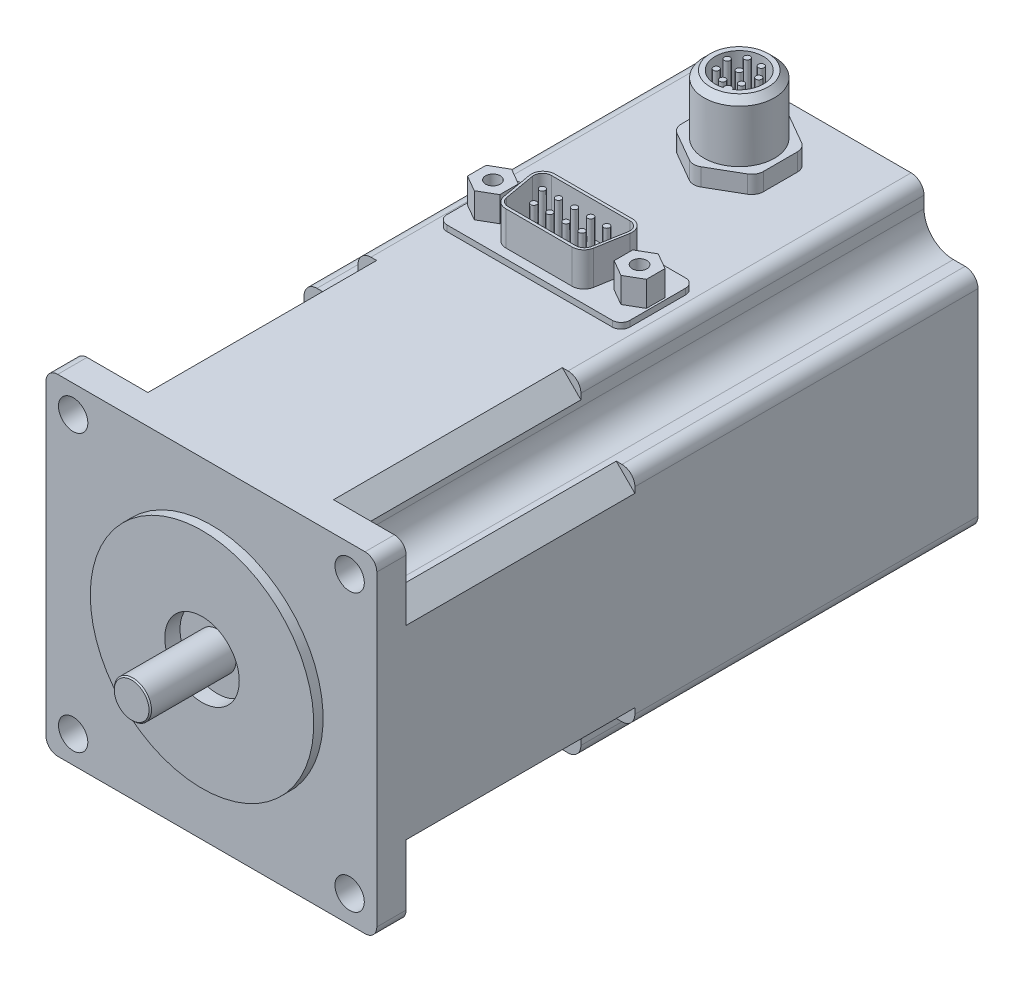
SolidWorks part; units mm, degrees
ref_plane "Front Plane" through (0, 0, 0) normal (0, 0, 1) x (1, 0, 0)
ref_plane "Top Plane" through (0, 0, 0) normal (0, 1, 0) x (1, 0, 0)
ref_plane "Right Plane" through (0, 0, 0) normal (1, 0, 0) x (0, 0, -1)
sketch "Sketch1" plane through (0, 0, 0) normal (0, 1, 0) x (1, 0, 0)
  line L0 (0, 0) -> (19.05, 0)
  line L1 (19.05, 0) -> (19.05, -1.6)
  line L2 (19.05, -1.6) -> (3.175, -1.6)
  line L3 (3.175, -1.6) -> (3.175, -13.6)
  line L4 (3.175, -13.6) -> (0, -13.6)
  line L5 (0, -13.6) -> (0, 0)
  line L6 (0, -13.6) -> (0, 0) construction
revolve "Revolve1" add sketch "Sketch1" angle 360 about L6 reverse direction yes
sketch "Sketch2" plane through (0, 0, 0) normal (0, 0, 1) x (1, 0, 0)
  line L0 (-26.2, -28.2) -> (26.2, -28.2)
  line L1 (28.2, -26.2) -> (28.2, 26.2)
  line L2 (26.2, 28.2) -> (-26.2, 28.2)
  line L3 (-28.2, 26.2) -> (-28.2, -26.2)
  arc A0 (-28.2, -26.2) -> (-26.2, -28.2) centre (-26.2, -26.2) ccw
  arc A1 (26.2, -28.2) -> (28.2, -26.2) centre (26.2, -26.2) ccw
  arc A2 (28.2, 26.2) -> (26.2, 28.2) centre (26.2, 26.2) ccw
  arc A3 (-26.2, 28.2) -> (-28.2, 26.2) centre (-26.2, 26.2) ccw
extrude "Boss-Extrude1" add sketch "Sketch2" against normal blind 70.5
ref_plane "Plane1" through (0, 0, -5) normal (0, 0, 1) x (1, 0, 0)
sketch "Sketch3" plane through (0, 0, -5) normal (0, 0, 1) x (1, 0, 0)
  line L0 (-37.6, -37.6) -> (37.6, -37.6)
  line L1 (37.6, -37.6) -> (37.6, 37.6)
  line L2 (37.6, 37.6) -> (-37.6, 37.6)
  line L3 (-37.6, 37.6) -> (-37.6, -37.6)
  line L4 (-26, -19) -> (-24, -19)
  line L5 (-19, -24) -> (-19, -26)
  line L6 (-16.8, -28.2) -> (16.8, -28.2)
  line L7 (19, -26) -> (19, -24)
  line L8 (24, -19) -> (26, -19)
  line L9 (28.2, -16.8) -> (28.2, 16.8)
  line L10 (26, 19) -> (24, 19)
  line L11 (19, 24) -> (19, 26)
  line L12 (16.8, 28.2) -> (-16.8, 28.2)
  line L13 (-19, 26) -> (-19, 24)
  line L14 (-24, 19) -> (-26, 19)
  line L15 (-28.2, 16.8) -> (-28.2, -16.8)
  arc A0 (-28.2, -16.8) -> (-26, -19) centre (-26, -16.8) ccw
  arc A1 (-24, -19) -> (-19, -24) centre (-24, -24) cw
  arc A2 (-19, -26) -> (-16.8, -28.2) centre (-16.8, -26) ccw
  arc A3 (16.8, -28.2) -> (19, -26) centre (16.8, -26) ccw
  arc A4 (19, -24) -> (24, -19) centre (24, -24) cw
  arc A5 (26, -19) -> (28.2, -16.8) centre (26, -16.8) ccw
  arc A6 (28.2, 16.8) -> (26, 19) centre (26, 16.8) ccw
  arc A7 (24, 19) -> (19, 24) centre (24, 24) cw
  arc A8 (19, 26) -> (16.8, 28.2) centre (16.8, 26) ccw
  arc A9 (-16.8, 28.2) -> (-19, 26) centre (-16.8, 26) ccw
  arc A10 (-19, 24) -> (-24, 19) centre (-24, 24) cw
  arc A11 (-26, 19) -> (-28.2, 16.8) centre (-26, 16.8) ccw
sketch "Sketch4" plane through (0, 0, 0) normal (0, 0, 1) x (1, 0, 0)
  circle A0 centre (23.57, -23.57) radius 2.5
extrude "Cut-Extrude1" cut sketch "Sketch4" against normal blind 5
sketch "Sketch5" plane through (0, 0, 0) normal (0, 0, 1) x (1, 0, 0)
  circle A0 centre (23.57, 23.57) radius 2.5
extrude "Cut-Extrude2" cut sketch "Sketch5" against normal blind 5
sketch "Sketch6" plane through (0, 0, 0) normal (0, 0, 1) x (1, 0, 0)
  circle A0 centre (-23.57, -23.57) radius 2.5
extrude "Cut-Extrude3" cut sketch "Sketch6" against normal blind 5
sketch "Sketch7" plane through (0, 0, 0) normal (0, 0, 1) x (1, 0, 0)
  circle A0 centre (-23.57, 23.57) radius 2.5
extrude "Cut-Extrude4" cut sketch "Sketch7" against normal blind 5
extrude "Cut-Extrude5" cut sketch "Sketch3" against normal blind 65.5
sketch "Sketch8" plane through (0, 0, -5) normal (0, 0, 1) x (1, 0, 0)
  line L0 (-37.6, 37.6) -> (-37.6, -37.6)
  line L1 (-37.6, -37.6) -> (37.6, -37.6)
  line L2 (37.6, -37.6) -> (37.6, 37.6)
  line L3 (37.6, 37.6) -> (-37.6, 37.6)
  line L4 (-28.2, -15.8256) -> (-15.8256, -28.2)
  line L5 (-15.8256, -28.2) -> (15.8256, -28.2)
  line L6 (15.8256, -28.2) -> (28.2, -15.8256)
  line L7 (28.2, -15.8256) -> (28.2, 15.8256)
  line L8 (28.2, 15.8256) -> (15.8256, 28.2)
  line L9 (15.8256, 28.2) -> (-15.8256, 28.2)
  line L10 (-15.8256, 28.2) -> (-28.2, 15.8256)
  line L11 (-28.2, 15.8256) -> (-28.2, -15.8256)
extrude "Cut-Extrude6" cut sketch "Sketch8" against normal blind 39
ref_plane "Plane2" through (0, 0, -70.5) normal (0, 0, 1) x (1, 0, 0)
sketch "Sketch9" plane through (0, 0, -70.5) normal (0, 0, 1) x (1, 0, 0)
  line L0 (-26, -19) -> (-24, -19)
  line L1 (-19, -24) -> (-19, -26)
  line L2 (-16.8, -28.2) -> (16.8, -28.2)
  line L3 (19, -26) -> (19, -24)
  line L4 (24, -19) -> (26, -19)
  line L5 (28.2, -16.8) -> (28.2, 16.8)
  line L6 (26, 19) -> (24, 19)
  line L7 (19, 24) -> (19, 26)
  line L8 (16.8, 28.2) -> (-16.8, 28.2)
  line L9 (-19, 26) -> (-19, 24)
  line L10 (-24, 19) -> (-26, 19)
  line L11 (-28.2, 16.8) -> (-28.2, -16.8)
  arc A0 (-28.2, -16.8) -> (-26, -19) centre (-26, -16.8) ccw
  arc A1 (-24, -19) -> (-19, -24) centre (-24, -24) cw
  arc A2 (-19, -26) -> (-16.8, -28.2) centre (-16.8, -26) ccw
  arc A3 (16.8, -28.2) -> (19, -26) centre (16.8, -26) ccw
  arc A4 (19, -24) -> (24, -19) centre (24, -24) cw
  arc A5 (26, -19) -> (28.2, -16.8) centre (26, -16.8) ccw
  arc A6 (28.2, 16.8) -> (26, 19) centre (26, 16.8) ccw
  arc A7 (24, 19) -> (19, 24) centre (24, 24) cw
  arc A8 (19, 26) -> (16.8, 28.2) centre (16.8, 26) ccw
  arc A9 (-16.8, 28.2) -> (-19, 26) centre (-16.8, 26) ccw
  arc A10 (-19, 24) -> (-24, 19) centre (-24, 24) cw
  arc A11 (-26, 19) -> (-28.2, 16.8) centre (-26, 16.8) ccw
extrude "Boss-Extrude2" add sketch "Sketch9" against normal blind 32
ref_plane "Plane3" through (0, 28.2, 0) normal (0, 1, 0) x (1, 0, 0)
sketch "Sketch10" plane through (0, 28.2, 0) normal (0, 1, 0) x (1, 0, 0)
  line L0 (-15.6, 65.25) -> (-15.6, 55.75)
  line L1 (-14.1, 54.25) -> (14.1, 54.25)
  line L2 (15.6, 55.75) -> (15.6, 65.25)
  line L3 (14.1, 66.75) -> (-14.1, 66.75)
  arc A0 (-15.6, 55.75) -> (-14.1, 54.25) centre (-14.1, 55.75) ccw
  arc A1 (14.1, 54.25) -> (15.6, 55.75) centre (14.1, 55.75) ccw
  arc A2 (15.6, 65.25) -> (14.1, 66.75) centre (14.1, 65.25) ccw
  arc A3 (-14.1, 66.75) -> (-15.6, 65.25) centre (-14.1, 65.25) ccw
extrude "Boss-Extrude3" add sketch "Sketch10" along normal blind 1
sketch "Sketch11" plane through (0, 28.2, 0) normal (0, 1, 0) x (1, 0, 0)
  line L0 (-8.5695, 62.8027) -> (-7.635, 57.5027)
  line L1 (-5.6654, 55.85) -> (5.6654, 55.85)
  line L2 (7.635, 57.5027) -> (8.5695, 62.8027)
  line L3 (6.5999, 65.15) -> (-6.5999, 65.15)
  arc A0 (-6.5999, 65.15) -> (-8.5695, 62.8027) centre (-6.5999, 63.15) ccw
  arc A1 (-7.635, 57.5027) -> (-5.6654, 55.85) centre (-5.6654, 57.85) ccw
  arc A2 (5.6654, 55.85) -> (7.635, 57.5027) centre (5.6654, 57.85) ccw
  arc A3 (8.5695, 62.8027) -> (6.5999, 65.15) centre (6.5999, 63.15) ccw
extrude "Boss-Extrude4" add sketch "Sketch11" along normal blind 6.8
ref_plane "Plane4" through (0, 29.2, 0) normal (0, 1, 0) x (1, 0, 0)
sketch "Sketch12" plane through (0, 29.2, 0) normal (0, 1, 0) x (1, 0, 0)
  line L0 (-8.173, 62.8895) -> (-7.2385, 57.5895)
  line L1 (-5.7613, 56.35) -> (5.7613, 56.35)
  line L2 (7.2385, 57.5895) -> (8.173, 62.8895)
  line L3 (6.6958, 64.65) -> (-6.6958, 64.65)
  arc A0 (-6.6958, 64.65) -> (-8.173, 62.8895) centre (-6.6958, 63.15) ccw
  arc A1 (-7.2385, 57.5895) -> (-5.7613, 56.35) centre (-5.7613, 57.85) ccw
  arc A2 (5.7613, 56.35) -> (7.2385, 57.5895) centre (5.7613, 57.85) ccw
  arc A3 (8.173, 62.8895) -> (6.6958, 64.65) centre (6.6958, 63.15) ccw
  circle A4 centre (5.48, 61.92) radius 0.5
  circle A5 centre (4.11, 59.08) radius 0.5
  circle A6 centre (2.74, 61.92) radius 0.5
  circle A7 centre (1.37, 59.08) radius 0.5
  circle A8 centre (0, 61.92) radius 0.5
  circle A9 centre (-1.37, 59.08) radius 0.5
  circle A10 centre (-2.74, 61.92) radius 0.5
  circle A11 centre (-4.11, 59.08) radius 0.5
  circle A12 centre (-5.48, 61.92) radius 0.5
extrude "Cut-Extrude7" cut sketch "Sketch12" along normal blind 5.8
sketch "Sketch13" plane through (0, 28.2, 0) normal (0, 1, 0) x (1, 0, 0)
  line L0 (9.75, 58.9123) -> (12.5, 57.3246)
  line L1 (12.5, 57.3246) -> (15.25, 58.9123)
  line L2 (15.25, 58.9123) -> (15.25, 62.0877)
  line L3 (15.25, 62.0877) -> (12.5, 63.6754)
  line L4 (12.5, 63.6754) -> (9.75, 62.0877)
  line L5 (9.75, 62.0877) -> (9.75, 58.9123)
  circle A0 centre (12.5, 60.5) radius 1.25
extrude "Boss-Extrude5" add sketch "Sketch13" along normal blind 5.3
sketch "Sketch14" plane through (0, 28.2, 0) normal (0, 1, 0) x (1, 0, 0)
  line L0 (-15.25, 58.9123) -> (-12.5, 57.3246)
  line L1 (-12.5, 57.3246) -> (-9.75, 58.9123)
  line L2 (-9.75, 58.9123) -> (-9.75, 62.0877)
  line L3 (-9.75, 62.0877) -> (-12.5, 63.6754)
  line L4 (-12.5, 63.6754) -> (-15.25, 62.0877)
  line L5 (-15.25, 62.0877) -> (-15.25, 58.9123)
  circle A0 centre (-12.5, 60.5) radius 1.25
extrude "Boss-Extrude6" add sketch "Sketch14" along normal blind 5.3
ref_plane "Plane5" through (0, 0, -102.5) normal (0, 0, 1) x (1, 0, 0)
sketch "Sketch15" plane through (0, 0, -102.5) normal (0, 0, 1) x (1, 0, 0)
  line L0 (-19, 8.5) -> (-19, -8.5)
  line L1 (-19, -8.5) -> (19, -8.5)
  line L2 (19, -8.5) -> (19, 8.5)
  line L3 (19, 8.5) -> (-19, 8.5)
extrude "Cut-Extrude8" cut sketch "Sketch15" along normal blind 0.1
sketch "Sketch16" plane through (0, 28.2, 0) normal (0, 1, 0) x (1, 0, 0)
  line L0 (-6, 85.3812) -> (-1, 82.4944)
  line L1 (1, 82.4944) -> (6, 85.3812)
  line L2 (7, 87.1132) -> (7, 92.8868)
  line L3 (6, 94.6188) -> (1, 97.5056)
  line L4 (-1, 97.5056) -> (-6, 94.6188)
  line L5 (-7, 92.8868) -> (-7, 87.1132)
  arc A0 (-7, 87.1132) -> (-6, 85.3812) centre (-5, 87.1132) ccw
  arc A1 (-1, 82.4944) -> (1, 82.4944) centre (0, 84.2265) ccw
  arc A2 (6, 85.3812) -> (7, 87.1132) centre (5, 87.1132) ccw
  arc A3 (7, 92.8868) -> (6, 94.6188) centre (5, 92.8868) ccw
  arc A4 (1, 97.5056) -> (-1, 97.5056) centre (0, 95.7735) ccw
  arc A5 (-6, 94.6188) -> (-7, 92.8868) centre (-5, 92.8868) ccw
extrude "Boss-Extrude7" add sketch "Sketch16" along normal blind 3
sketch "Sketch17" plane through (0, 0, 0) normal (1, 0, 0) x (0, 0, -1)
  line L0 (90, 30.2) -> (84, 30.2)
  line L1 (84, 30.2) -> (84, 40.1265)
  line L2 (84, 40.1265) -> (85.0735, 41.2)
  line L3 (85.0735, 41.2) -> (90, 41.2)
  line L4 (90, 41.2) -> (90, 30.2)
  line L5 (90, 41.2) -> (90, 30.2) construction
revolve "Revolve2" add sketch "Sketch17" angle 360 about L5 reverse direction yes
cosmetic thread "Cosmetic Thread1" parameters "D1"=10, "D2"=9.853
ref_plane "Plane6" through (0, 41.2, 0) normal (0, 1, 0) x (1, 0, 0)
sketch "Sketch18" plane through (0, 41.2, 0) normal (0, 1, 0) x (1, 0, 0)
  arc A0 (2.2556, 86.5762) -> (1.1729, 86.0713) centre (0, 90) ccw
  arc A1 (1.1729, 86.0713) -> (2.2556, 86.5762) centre (1.6905, 86.3748) cw
  circle A2 centre (-0.0349, 87.2002) radius 0.5
  circle A3 centre (2.1672, 88.2271) radius 0.5
  circle A4 centre (-2.2107, 88.2817) radius 0.5
  circle A5 centre (0, 90) radius 0.5
  circle A6 centre (2.7374, 90.589) radius 0.5
  circle A7 centre (-2.7218, 90.657) radius 0.5
  circle A8 centre (1.2462, 92.5074) radius 0.5
  circle A9 centre (-1.1833, 92.5377) radius 0.5
extrude "Cut-Extrude9" cut sketch "Sketch18" against normal blind 8
sketch "Sketch19" plane through (0, 0, 0) normal (1, 0, 0) x (0, 0, -1)
  line L0 (-13.6, 6.35) -> (-13.6, 2.9629)
  line L1 (-13.6, 2.9629) -> (-13.3879, 3.175)
  line L2 (-13.3879, 3.175) -> (1, 3.175)
  line L3 (1, 3.175) -> (1, 6.35)
  line L4 (1, 6.35) -> (-13.6, 6.35)
  line L5 (50, 0) -> (-50, 0) construction
revolve "Cut-Revolve1" cut sketch "Sketch19" angle 360 about L5 reverse direction yes
ref_plane "Plane7" through (0, 0, -5) normal (0, 0, 1) x (1, 0, 0)
ref_plane "Plane8" through (0, 31.2, 0) normal (0, 1, 0) x (1, 0, 0)
ref_plane "ANBAU XY" through (0, 0, 0) normal (0, 0, -1) x (-1, 0, 0)
ref_plane "ANBAU XZ" through (0, 0, 0) normal (0, 1, 0) x (1, 0, 0)
ref_plane "ANBAU YZ" through (0, 0, 0) normal (1, 0, 0) x (0, 0, -1)
ref_axis "ANBAU X" through (-80.9, 0, 0) along (1, 0, 0)
ref_axis "ANBAU Y" through (0, 50, 0) along (0, -1, 0)
ref_axis "ANBAU Z" through (0, 0, -80.9) along (0, 0, 1)
sketch3d "ANBAU"
  point P0 (0, 0, 0)
ref_plane "EL XY" through (0, 31.2, 0) normal (0, -1, 0) x (-1, 0, 0)
ref_plane "EL XZ" through (0, 0, -90) normal (0, 0, -1) x (-1, 0, 0)
ref_plane "EL YZ" through (0, 0, 0) normal (1, 0, 0) x (0, 0, -1)
ref_axis "EL X" through (-80.9, 31.2, -90) along (1, 0, 0)
ref_axis "EL Y" through (0, 31.2, -50) along (0, 0, 1)
ref_axis "EL Z" through (0, -50, -90) along (0, 1, 0)
sketch3d "EL"
  point P0 (0, 31.2, -90)
ref_plane "ML XY" through (0, 29.2, 0) normal (0, -1, 0) x (-1, 0, 0)
ref_plane "ML XZ" through (0, 0, -62.5) normal (0, 0, -1) x (-1, 0, 0)
ref_plane "ML YZ" through (0, 0, 0) normal (1, 0, 0) x (0, 0, -1)
ref_axis "ML X" through (-80.9, 29.2, -62.5) along (1, 0, 0)
ref_axis "ML Y" through (0, 29.2, -50) along (0, 0, 1)
ref_axis "ML Z" through (0, -50, -62.5) along (0, 1, 0)
sketch3d "ML"
  point P0 (0, 29.2, -62.5)
ref_plane "SCREWS 1 XY" through (0, 0, -5) normal (0, 0, 1) x (1, 0, 0)
ref_plane "SCREWS 1 XZ" through (0, 23.57, 0) normal (0, -1, 0) x (-1, 0, 0)
ref_plane "SCREWS 1 YZ" through (23.57, 0, 0) normal (1, 0, 0) x (0, 0, -1)
ref_axis "SCREWS 1 X" through (-80.9, 23.57, -5) along (1, 0, 0)
ref_axis "SCREWS 1 Y" through (23.57, -50, -5) along (0, 1, 0)
ref_axis "SCREWS 1 Z" through (23.57, 23.57, 80.9) along (0, 0, -1)
sketch3d "SCREWS 1"
  point P0 (23.57, 23.57, -5)
ref_plane "SCREWS 2 XY" through (0, 0, -5) normal (0, 0, 1) x (1, 0, 0)
ref_plane "SCREWS 2 XZ" through (0, 23.57, 0) normal (0, -1, 0) x (-1, 0, 0)
ref_plane "SCREWS 2 YZ" through (-23.57, 0, 0) normal (1, 0, 0) x (0, 0, -1)
ref_axis "SCREWS 2 X" through (-80.9, 23.57, -5) along (1, 0, 0)
ref_axis "SCREWS 2 Y" through (-23.57, -50, -5) along (0, 1, 0)
ref_axis "SCREWS 2 Z" through (-23.57, 23.57, 80.9) along (0, 0, -1)
sketch3d "SCREWS 2"
  point P0 (-23.57, 23.57, -5)
ref_plane "SCREWS 3 XY" through (0, 0, -5) normal (0, 0, 1) x (1, 0, 0)
ref_plane "SCREWS 3 XZ" through (0, -23.57, 0) normal (0, -1, 0) x (-1, 0, 0)
ref_plane "SCREWS 3 YZ" through (-23.57, 0, 0) normal (1, 0, 0) x (0, 0, -1)
ref_axis "SCREWS 3 X" through (-80.9, -23.57, -5) along (1, 0, 0)
ref_axis "SCREWS 3 Y" through (-23.57, -50, -5) along (0, 1, 0)
ref_axis "SCREWS 3 Z" through (-23.57, -23.57, 80.9) along (0, 0, -1)
sketch3d "SCREWS 3"
  point P0 (-23.57, -23.57, -5)
ref_plane "SCREWS 4 XY" through (0, 0, -5) normal (0, 0, 1) x (1, 0, 0)
ref_plane "SCREWS 4 XZ" through (0, -23.57, 0) normal (0, -1, 0) x (-1, 0, 0)
ref_plane "SCREWS 4 YZ" through (23.57, 0, 0) normal (1, 0, 0) x (0, 0, -1)
ref_axis "SCREWS 4 X" through (-80.9, -23.57, -5) along (1, 0, 0)
ref_axis "SCREWS 4 Y" through (23.57, -50, -5) along (0, 1, 0)
ref_axis "SCREWS 4 Z" through (23.57, -23.57, 80.9) along (0, 0, -1)
sketch3d "SCREWS 4"
  point P0 (23.57, -23.57, -5)
other "Freeze***"
